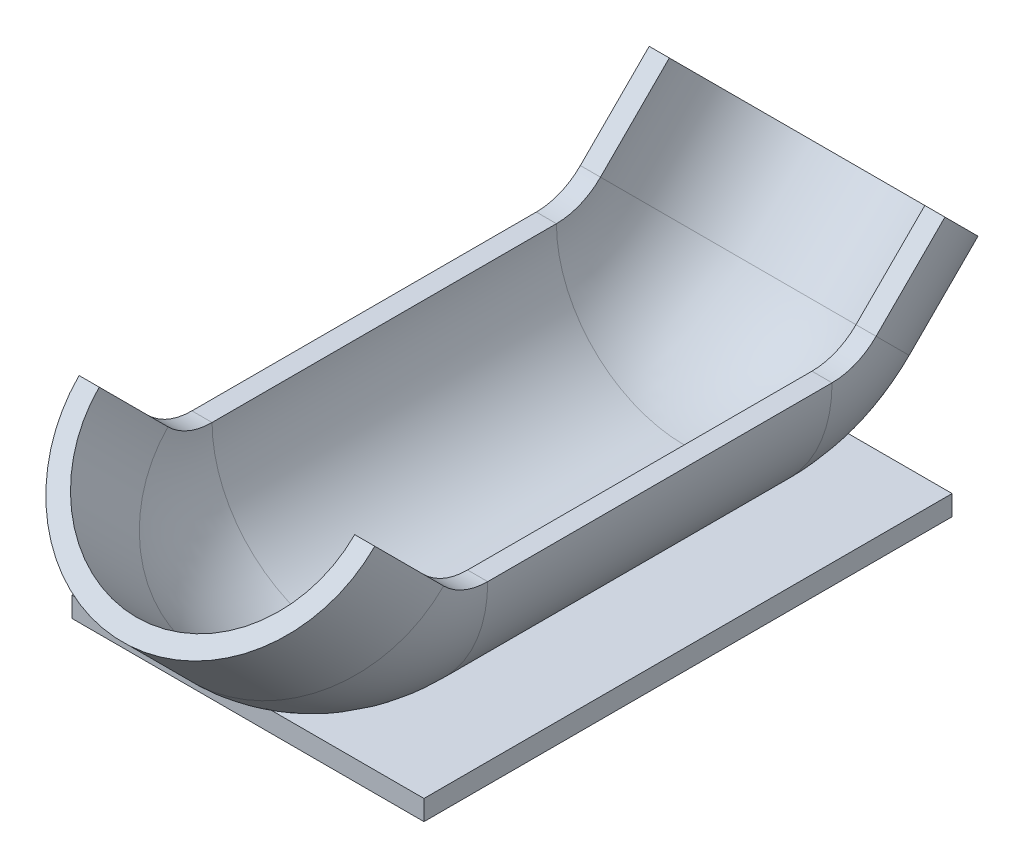
SolidWorks part; units mm, degrees
ref_plane "Front Plane" through (0, 0, 0) normal (0, 0, 1) x (1, 0, 0)
ref_plane "Top Plane" through (0, 0, 0) normal (0, 1, 0) x (1, 0, 0)
ref_plane "Right Plane" through (0, 0, 0) normal (1, 0, 0) x (0, 0, -1)
sketch "Sketch1" plane through (0, 0, 0) normal (0, 0, 1) x (1, 0, 0)
  line L2 (-25.4, 0) -> (-29.4, 0)
  line L3 (25.4, 0) -> (29.4, 0)
  line L4 (-29.1266, 4) -> (29.1266, 4) construction
  line L5 (-25.4, 0) -> (25.4, 0) construction
  arc A0 (-25.4, 0) -> (25.4, 0) centre (0, 0) ccw
  arc A1 (-29.4, 0) -> (29.4, 0) centre (0, 0) ccw
  arc A2 (-29.1266, 4) -> (29.1266, 4) centre (0, 0) ccw construction
  dimension "D1" = 50.8
  dimension "D2" = 4
sketch "Sketch3" plane through (0, 0, 0) normal (1, 0, 0) x (0, 0, -1)
  line L0 (-34.2315, -27.6128) -> (34.2315, -27.6128)
  line L2 (0, 0) -> (0, -29.4) construction
  line L3 (62.5157, -15.8971) -> (76.2, -2.2128)
  line L4 (0, -27.6128) -> (0, 7.0661) construction
  line L5 (-62.5157, -15.8971) -> (-76.2, -2.2128)
  arc A0 (34.2315, -27.6128) -> (62.5157, -15.8971) centre (34.2315, 12.3872) ccw
  arc A1 (-34.2315, -27.6128) -> (-62.5157, -15.8971) centre (-34.2315, 12.3872) cw
  point P7 (50.8, -27.6128)
  point P14 (-50.8, -27.6128)
  dimension "D3" = 40
  dimension "D1" = 45
  dimension "D2" = 50.8
  dimension "D4" = 25.4
sweep "Sweep2" add profiles "Sketch1" path "Sketch3"
sketch "Sketch4" plane through (0, 0, 0) normal (0, 1, 0) x (1, 0, 0)
  circle A0 centre (-26.5, 45) radius 3.175
  circle A1 centre (26.5, 45) radius 3.175
  circle A2 centre (-26.5, -45) radius 3.175
  circle A3 centre (26.5, -45) radius 3.175
  point P8 (0, 0)
  point P9 (0, 0)
  point P10 (0, 0)
  point P11 (0, 0)
  dimension "D3" = 6.35
  dimension "D4" = 6.35
  dimension "D5" = 6.35
  dimension "D6" = 6.35
  dimension "D1" = 53
  dimension "D2" = 90
  dimension "D7" = 45
  dimension "D8" = 26.5
sketch "Sketch5" plane through (0, 0, 0) normal (0, 1, 0) x (1, 0, 0)
  line L1 (-35, 52.5) -> (35, 52.5)
  line L2 (-35, 52.5) -> (-35, -52.5)
  line L3 (-35, -52.5) -> (35, -52.5)
  line L4 (35, 52.5) -> (35, -52.5)
  dimension "D1" = 105
  dimension "D2" = 52.5
  dimension "D3" = 70
  dimension "D4" = 35
ref_plane "Plane2" through (0, -29.4, 0) normal (0, -1, 0) x (-1, 0, 0)
sketch "Sketch6" plane through (0, -29.4, 0) normal (0, -1, 0) x (-1, 0, 0)
  line L0 (-35, 52.5) -> (35, 52.5)
  line L1 (-35, 52.5) -> (-35, -52.5)
  line L2 (-35, -52.5) -> (35, -52.5)
  line L3 (35, 52.5) -> (35, -52.5)
  point P7 (-7.9941, 52.5)
  dimension "D1" = 35
  dimension "D2" = 52.5
  dimension "D3" = 70
  dimension "D4" = 105
extrude "Boss-Extrude1" add sketch "Sketch6" against normal blind 4
equation "\"D7@Sketch4\"=90/2"
equation "\"D8@Sketch4\"=53/2"
equation "\"D2@Sketch5\"=105/2"
equation "\"D4@Sketch5\"=35"
